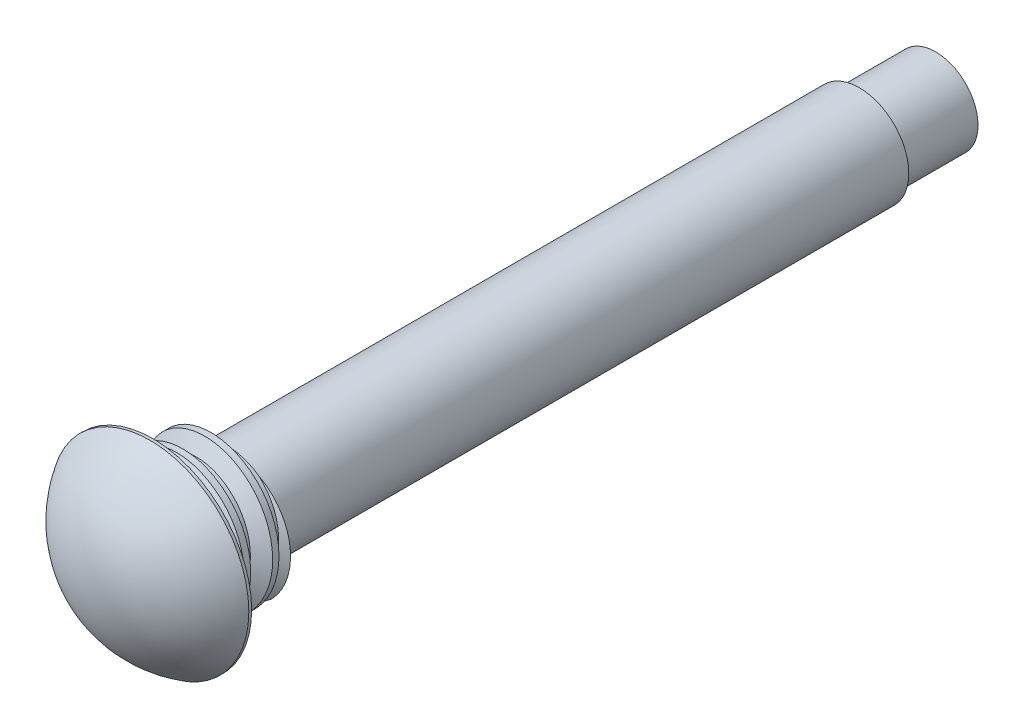
SolidWorks part; units mm, degrees
ref_plane "Front Plane" through (0, 0, 0) normal (0, 0, 1) x (1, 0, 0)
ref_plane "Top Plane" through (0, 0, 0) normal (0, 1, 0) x (1, 0, 0)
ref_plane "Right Plane" through (0, 0, 0) normal (1, 0, 0) x (0, 0, -1)
sketch "Sketch2" plane through (0, 0, 0) normal (0, 0, 1) x (1, 0, 0)
  circle A0 centre (0, 0) radius 3.175
curve "Helix/Spiral1" pitch 1.27 height 3.302 radius 3.175 left hand yes centre (0, 0, 0) axis (0, 0, 1) start towards (0, 1, 0)
sketch "Sketch3" plane through (0, 0, 0) normal (0, 0, 1) x (1, 0, 0)
  circle A0 centre (0, 0) radius 3.175
extrude "Boss-Extrude1" add sketch "Sketch3" along normal blind 3.302 contours A0
sketch "Sketch5" plane through (0, 0, 0) normal (1, 0, 0) x (0, 0, -1)
  line L0 (0.127, 2.54) -> (0.4936, 3.175)
  line L1 (0.4936, 3.175) -> (-0.4936, 3.175)
  line L2 (-0.4936, 3.175) -> (-0.127, 2.54)
  line L3 (-0.127, 2.54) -> (0.127, 2.54)
  line L4 (0, 3.175) -> (0, 2.54) construction
  dimension "D1" = 0.635
  dimension "D2" = 0.254
  dimension "D3" = 60
sweep "Cut-Sweep1" cut profiles "Sketch5" path "Helix/Spiral1" align with end faces yes
sketch "Sketch8" plane through (0, 0, 0) normal (0, 0, 1) x (1, 0, 0)
  circle A0 centre (0, 0) radius 2.2225
extrude "Boss-Extrude3" add sketch "Sketch8" against normal blind 28.448
sketch "Sketch10" plane through (0, 0, -28.448) normal (0, 0, -1) x (-1, 0, 0)
  circle A0 centre (0, 0) radius 1.905
extrude "Boss-Extrude5" add sketch "Sketch10" along normal blind 3.429
sketch "Sketch11" plane through (0, 0, 3.302) normal (0, 0, 1) x (1, 0, 0)
  circle A0 centre (0, 0) radius 4.445
extrude "Boss-Extrude6" add sketch "Sketch11" along normal blind 0.127
dome "Dome1" faces to dome 1 distance 2.54 reverse direction no elliptical dome no face at (4.445, 0, 3.429) parameters "D1"=2.54
